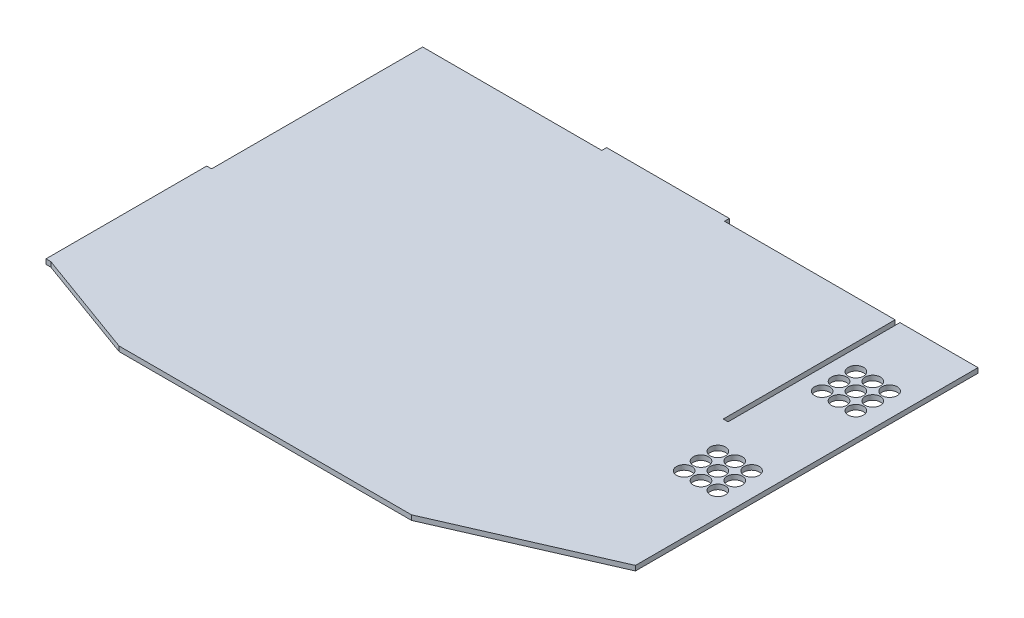
SolidWorks part; units mm, degrees
material "6061-T6 (SS)"
ref_plane "X-Y Datum" through (0, 0, 0) normal (0, 0, 1) x (1, 0, 0)
ref_plane "X-Z Datum" through (0, 0, 0) normal (0, 1, 0) x (1, 0, 0)
ref_plane "Y-Z Datum" through (0, 0, 0) normal (1, 0, 0) x (0, 0, -1)
sketch "Sketch1" plane through (0, 0, 0) normal (0, 0, 1) x (1, 0, 0)
  line L1 (-154.0556, -1.5875) -> (154.0556, -1.5875)
  line L2 (-154.0556, -1.5875) -> (-154.0556, 1.5875)
  line L3 (-154.0556, 1.5875) -> (154.0556, 1.5875)
  line L4 (154.0556, -1.5875) -> (154.0556, 1.5875)
  line L5 (-154.0556, -1.5875) -> (154.0556, 1.5875) construction
  line L6 (-154.0556, 1.5875) -> (154.0556, -1.5875) construction
  point P0 (0, 0)
  dimension "D1" = 3.175
  dimension "D2" = 308.1112
extrude "Boss-Extrude1" add sketch "Sketch1" along normal blind 267.83
sketch "Sketch3" plane through (154.0556, 0, 0) normal (1, 0, 0) x (0, 0, -1)
  line L0 (-267.83, 1.5875) -> (0, 1.5875) construction
  line L1 (-267.83, -1.5875) -> (-112.128, -1.5875)
  line L2 (-267.83, -1.5875) -> (-267.83, 1.5875)
  line L3 (-267.83, 1.5875) -> (-112.128, 1.5875)
  line L4 (-112.128, -1.5875) -> (-112.128, 1.5875)
  dimension "D1" = 155.702
extrude "Boss-Extrude3" add sketch "Sketch3" along normal blind 3.175
sketch "Sketch4" plane through (0, 0, 267.83) normal (0, 0, 1) x (1, 0, 0)
  line L1 (157.2306, -1.5875) -> (208.1043, -1.5875)
  line L2 (157.2306, -1.5875) -> (157.2306, 1.5875)
  line L3 (157.2306, 1.5875) -> (208.1043, 1.5875)
  line L4 (208.1043, -1.5875) -> (208.1043, 1.5875)
  dimension "D1" = 3.175
  dimension "D2" = 50.8737
extrude "Boss-Extrude4" add sketch "Sketch4" against normal blind 267.83
sketch "Sketch6" plane through (0, 1.5875, 0) normal (0, 1, 0) x (1, 0, 0)
  line L0 (106.5043, -267.83) -> (106.5043, -223.38)
  line L1 (208.1043, -267.83) -> (-154.0556, -267.83) construction
  line L2 (208.1043, -223.38) -> (106.5043, -223.38)
  line L3 (208.1043, 0) -> (208.1043, -267.83) construction
  line L4 (106.5043, -267.83) -> (208.1043, -223.38)
  line M9 (-154.0556, -267.83) -> (208.1043, -267.83)
  line M10 (208.1043, -267.83) -> (208.1043, 0)
  dimension "D1" = 44.45
  dimension "D2" = 101.6
extrude "Cut-Extrude1" cut sketch "Sketch6" against normal through all contours L4 M9 M10 region at (174.2376, 1.5875, 253.0133)
sketch "Sketch8" plane through (0, 0, 0) normal (0, 0, -1) x (-1, 0, 0)
  line L1 (37.216, 1.5875) -> (-42.784, 1.5875)
  line L2 (37.216, 1.5875) -> (37.216, -1.5875)
  line L3 (37.216, -1.5875) -> (-42.784, -1.5875)
  line L4 (-42.784, 1.5875) -> (-42.784, -1.5875)
extrude "Boss-Extrude6" add sketch "Sketch8" along normal blind 3.175
sketch "Sketch11" plane through (0, -1.5875, 0) normal (0, -1, 0) x (1, 0, 0)
  line L0 (-84.2056, 267.83) -> (-84.2056, 242.43)
  line L1 (-154.0556, 267.83) -> (106.5043, 267.83) construction
  line L2 (-154.0556, 242.43) -> (-84.2056, 242.43)
  line L3 (-154.0556, 267.83) -> (-154.0556, 0) construction
  line L4 (-154.0556, 242.43) -> (-84.2056, 267.83)
  line M4 (-154.0556, 267.83) -> (-154.0556, 0)
  line M18 (106.5043, 267.83) -> (-154.0556, 267.83)
  dimension "D1" = 69.85
  dimension "D2" = 25.4
extrude "Cut-Extrude3" cut sketch "Sketch11" against normal through all contours L4 M4 M18 region at (-130.7723, -1.5875, 259.3633)
sketch "Sketch13" plane through (-154.0556, 0, 0) normal (-1, 0, 0) x (0, 0, 1)
  line L1 (137.65, -1.598) -> (242.43, -1.598)
  line L2 (137.65, -1.598) -> (137.65, 1.5875)
  line L3 (137.65, 1.5875) -> (242.43, 1.5875)
  line L4 (242.43, -1.598) -> (242.43, 1.5875)
extrude "Boss-Extrude7" add sketch "Sketch13" along normal blind 3.175
sketch "Sketch14" plane through (0, 1.5875, 0) normal (0, 1, 0) x (1, 0, 0)
  line L0 (182.6674, 0) -> (182.6674, -201.027)
  line L1 (208.1043, 0) -> (157.2306, 0) construction
  line L3 (162.6674, -197.0069) -> (202.6674, -197.0069)
  line L4 (162.6674, -197.0069) -> (162.6674, -4.0201)
  line L5 (162.6674, -4.0201) -> (202.6674, -4.0201)
  line L6 (202.6674, -197.0069) -> (202.6674, -4.0201)
  line L7 (162.6674, -197.0069) -> (202.6674, -4.0201) construction
  line L8 (162.6674, -4.0201) -> (202.6674, -197.0069) construction
  circle A0 centre (170.5896, -42.1201) radius 5
  point P4 (182.6674, -100.5135)
  dimension "D3" = 10
  dimension "D1" = 40
  dimension "D2" = 7.9222
  dimension "D4" = 38.1
extrude "Cut-Extrude4" cut sketch "Sketch14" against normal through all contours A0 region at (170.5896, 1.5875, 42.1201)
pattern_linear "LPattern1" count 3 spacing 11 along (1, 0, 0) of "Cut-Extrude4"
pattern_linear "LPattern2" count 3 spacing 11 along (0, 0, 1) of "LPattern1"
sketch "Sketch15" plane through (0, 1.5875, 0) normal (0, 1, 0) x (1, 0, 0)
  line L0 (170.5896, -42.1201) -> (170.5896, -132.1284) construction
  circle A0 centre (170.5896, -132.1284) radius 5
  dimension "D1" = 10
extrude "Cut-Extrude5" cut sketch "Sketch15" against normal through all
pattern_linear "LPattern3" count 3 spacing 11 along (1, 0, 0) of "Cut-Extrude5"
pattern_linear "LPattern4" count 3 spacing 11 along (0, 0, 1) of "LPattern3"
